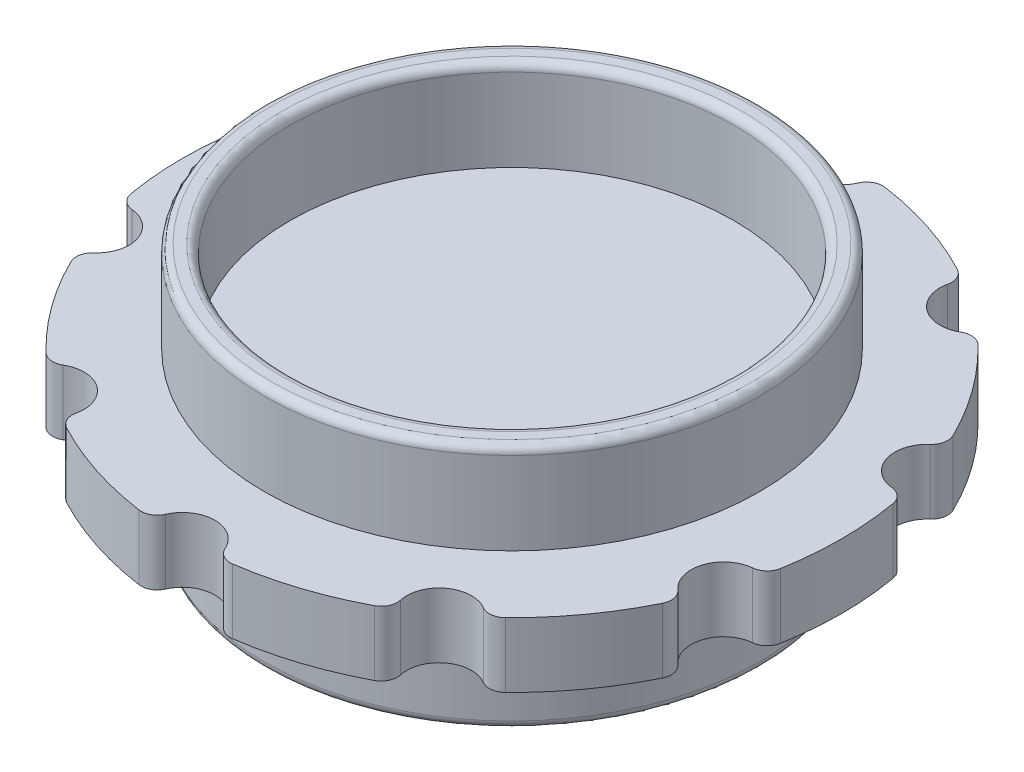
SolidWorks part; units mm, degrees
ref_plane "前视基准面" through (0, 0, 0) normal (0, 0, 1) x (1, 0, 0)
ref_plane "上视基准面" through (0, 0, 0) normal (0, 1, 0) x (1, 0, 0)
ref_plane "右视基准面" through (0, 0, 0) normal (1, 0, 0) x (0, 0, -1)
other "Configuration Table"
sketch "草图1" plane through (0, 0, 0) normal (0, 1, 0) x (1, 0, 0)
  circle A0 centre (0, 0) radius 15.3
  circle A1 centre (0, 0) radius 20.35
  circle A2 centre (0, 0) radius 13.7
  circle A3 centre (0, 20.35) radius 2
  dimension "D1" = 30.6
  dimension "D2" = 40.7
  dimension "D3" = 1.6
  dimension "D4" = 4
extrude "凸台-拉伸1" add sketch "草图1" along normal mid plane 15.2 contours A0 | A2
extrude "凸台-拉伸2" add sketch "草图1<3>" along normal mid plane 4 contours A1
sketch "草图1<3>" plane through (0, 0, 0) normal (0, 1, 0) x (1, 0, 0) same geometry as "草图1"
extrude "切除-拉伸1" cut sketch "草图1<4>" against normal through all both and the other way through all contours A3
sketch "草图1<4>" plane through (0, 0, 0) normal (0, 1, 0) x (1, 0, 0) same geometry as "草图1"
fillet "圆角1" radius 1 2 edges at (1.9976, 0, -20.2517) (-1.9976, 0, -20.2517)
pattern_circular "阵列(圆周)1" count 10 over 360 about axis through (0, 2, 0) along (0, -1, 0) of "切除-拉伸1", "圆角1"
fillet "圆角2" radius 0.5 4 edges at (0, -7.6, 13.7) (0, -7.6, 15.3) (0, 7.6, 13.7) (0, 7.6, 15.3)
